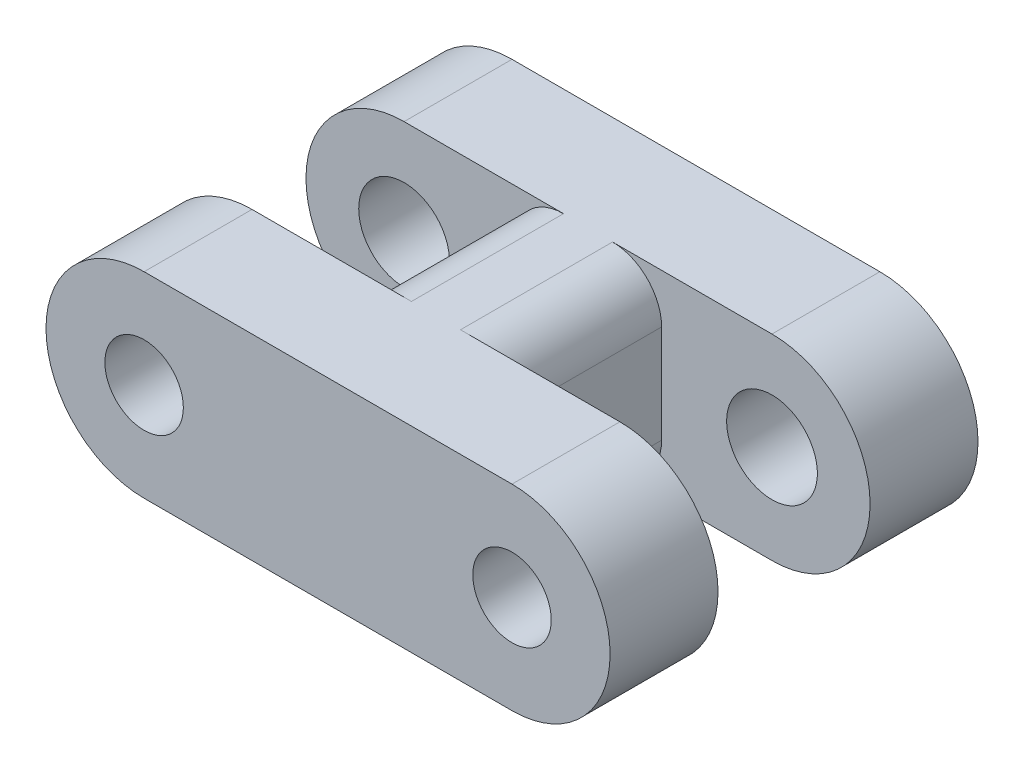
SolidWorks part; units mm, degrees
material "ABS"
ref_plane "Front Plane" through (0, 0, 0) normal (0, 0, 1) x (1, 0, 0)
ref_plane "Top Plane" through (0, 0, 0) normal (0, 1, 0) x (1, 0, 0)
ref_plane "Right Plane" through (0, 0, 0) normal (1, 0, 0) x (0, 0, -1)
sketch "Sketch1" plane through (0, 0, 0) normal (0, 0, 1) x (1, 0, 0)
  line L0 (-15, 0) -> (0, 0) construction
  line L1 (-15, 4) -> (0, 4)
  line L2 (0, -4) -> (-15, -4)
  line L3 (-13.1314, 7.2502) -> (0, 0) construction
  arc A0 (0, -4) -> (0, 4) centre (0, 0) ccw
  arc A1 (-15, 4) -> (-15, -4) centre (-15, 0) ccw
  circle A2 centre (0, 0) radius 1.6
  circle A3 centre (-15, 0) radius 1.6
  dimension "D1" = 8
  dimension "D2" = 3.2
extrude "Boss-Extrude1" add sketch "Sketch1" along normal mid plane 15
sketch "Sketch2" plane through (0, 0, 0) normal (0, 1, 0) x (1, 0, 0)
  line L1 (5.5, 3.1) -> (-4.5, 3.1)
  line L2 (5.5, 3.1) -> (5.5, -3.1)
  line L3 (5.5, -3.1) -> (-4.5, -3.1)
  line L4 (-4.5, 3.1) -> (-4.5, -3.1)
  line L5 (-20.5, 3.1) -> (-10.5, 3.1)
  line L6 (-20.5, 3.1) -> (-20.5, -3.1)
  line L7 (-20.5, -3.1) -> (-10.5, -3.1)
  line L8 (-10.5, 3.1) -> (-10.5, -3.1)
  point P8 (-4.5, 0)
  point P10 (-10.5, 0)
  dimension "D1" = 6.2
  dimension "D2" = 4.5
  dimension "D3" = 4.5
  dimension "D4" = 10
extrude "Cut-Extrude1" cut sketch "Sketch2" against normal through all both and the other way through all
ref_axis "Axis1" through (0, 0, 7.5) along (0, 0, -1)
ref_axis "Axis2" through (-15, 0, 7.5) along (0, 0, -1)
hole_wizard "Hole1" positions "Sketch3" profile "Sketch4" legacy
sketch "Sketch3" plane through (0, 0, -7.5) normal (0, 0, -1) x (-1, 0, 0)
  point P0 (0, 0)
  point P3 (15, 0)
sketch "Sketch4" plane through (0, 0, -7.5) normal (1, 0, 0) x (0, 1, 0)
  line L0 (0, 0) -> (0, 4.4)
  line L1 (0, 4.4) -> (1.85, 4.4)
  line L2 (1.85, 4.4) -> (1.85, 0)
  line L3 (1.85, 0) -> (0, 0)
  line L4 (0, 110) -> (0, -10) construction
  dimension "Diameter" = 3.7
  dimension "Depth" = 4.4
fillet "Fillet1" radius 2 4 edges at (-4.5, -4, 0) (-10.5, -4, 0) (-4.5, 4, 0) (-10.5, 4, 0)
